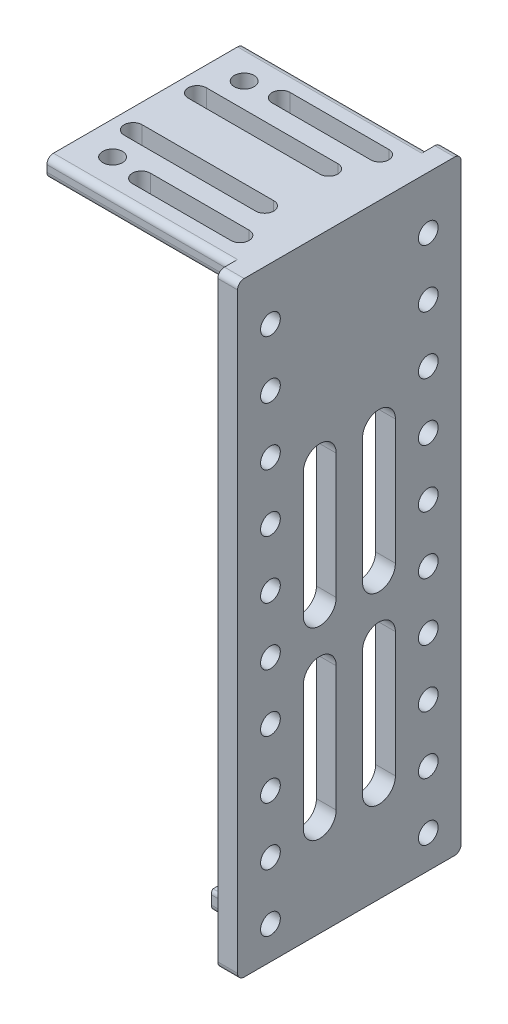
SolidWorks part; units mm, degrees
ref_plane "前视基准面" through (0, 0, 0) normal (0, 0, 1) x (1, 0, 0)
ref_plane "上视基准面" through (0, 0, 0) normal (0, 1, 0) x (1, 0, 0)
ref_plane "右视基准面" through (0, 0, 0) normal (1, 0, 0) x (0, 0, -1)
other "Configuration Table"
sketch "草图1" plane through (0, 0, 0) normal (0, 1, 0) x (1, 0, 0)
  line L0 (0, 12) -> (5, 12) construction
  line L1 (-1, 15) -> (1, 15) construction
  line L2 (-1, 15) -> (-1, 9) construction
  line L3 (-1, 9) -> (1, 9) construction
  line L4 (1, 15) -> (1, 9) construction
  line L5 (-1, 15) -> (1, 9) construction
  line L6 (-1, 9) -> (1, 15) construction
  line L7 (-1, -15) -> (1, -15) construction
  line L8 (-1, -15) -> (-1, -9) construction
  line L9 (-1, -9) -> (1, -9) construction
  line L10 (1, -15) -> (1, -9) construction
  line L11 (-1, -15) -> (1, -9) construction
  line L12 (-1, -9) -> (1, -15) construction
  line L13 (1, 14.5) -> (9, 14.5) construction
  line L14 (1, 14.5) -> (1, 9.5) construction
  line L15 (1, 9.5) -> (9, 9.5) construction
  line L16 (9, 14.5) -> (9, 9.5) construction
  line L17 (1, 14.5) -> (9, 9.5) construction
  line L18 (1, 9.5) -> (9, 14.5) construction
  line L19 (0, 0) -> (0, 9) construction
  line L20 (0, 12) -> (-5, 12) construction
  line L21 (-10.5, 0) -> (0, 0) construction
  line L22 (-9, 14.5) -> (-1, 14.5) construction
  line L23 (-9, 14.5) -> (-9, 9.5) construction
  line L24 (-9, 9.5) -> (-1, 9.5) construction
  line L25 (-1, 14.5) -> (-1, 9.5) construction
  line L26 (-9, 14.5) -> (-1, 9.5) construction
  line L27 (-9, 9.5) -> (-1, 14.5) construction
  line L33 (-12, -17) -> (-9, -17)
  line L34 (-12, -17) -> (-12, 17)
  line L35 (-12, 17) -> (-9, 17)
  line L36 (-9, -17) -> (-9, 17)
  line L37 (-12, -17) -> (-9, 17) construction
  line L38 (-12, 17) -> (-9, -17) construction
  circle A0 centre (0, 0) radius 9 construction
  circle A1 centre (0, 0) radius 12 construction
  point P4 (0, 12)
  point P9 (0, -12)
  point P14 (5, 12)
  point P28 (-10.5, 0)
  dimension "D1" = 18
  dimension "D2" = 24
  dimension "D3" = 6
  dimension "D4" = 2
  dimension "D5" = 8
  dimension "D6" = 5
  dimension "D7" = 8
  dimension "D8" = 5
  dimension "D9" = 3
  dimension "D10" = 5
extrude "凸台-拉伸1" add sketch "草图1" along normal blind 92
sketch "草图2" plane through (0, 0, 0) normal (0, -1, 0) x (1, 0, 0)
  line L0 (-12, -17) -> (-12, 17) construction
  line L1 (-20, 10) -> (-12, 10)
  line L2 (-20, 10) -> (-20, -10)
  line L3 (-20, -10) -> (-12, -10)
  line L4 (-12, 10) -> (-12, -10)
  line L5 (-20, 10) -> (-12, -10) construction
  line L6 (-20, -10) -> (-12, 10) construction
  line L7 (-16, 0) -> (0, 0) construction
  line L8 (-16, 5) -> (-16, -5) construction
  circle A0 centre (-16, 5) radius 1.5
  circle A1 centre (-16, -5) radius 1.5
  point P0 (-16, 0)
  point P14 (-16, 0)
  dimension "D5" = 3
  dimension "D1" = 20
  dimension "D2" = 20
  dimension "D3" = 10
  dimension "D4" = 16
extrude "凸台-拉伸2" add sketch "草图2" against normal blind 3
sketch "草图10" plane through (0, 92, 0) normal (0, 1, 0) x (1, 0, 0)
  line L0 (-26, 0) -> (0, 0) construction
  line L1 (-40, -15) -> (-12, -15)
  line L2 (-40, -15) -> (-40, 15)
  line L3 (-40, 15) -> (-12, 15)
  line L4 (-12, -15) -> (-12, 15)
  line L5 (-40, -15) -> (-12, 15) construction
  line L6 (-40, 15) -> (-12, -15) construction
  line L8 (-35, 10) -> (-35, -10) construction
  line L9 (-35, 0) -> (-26, 0) construction
  line L10 (-12, 17) -> (-12, -17) construction
  circle A0 centre (-35, 10) radius 1.5
  circle A1 centre (-35, -10) radius 1.5
  point P0 (-26, 0)
  dimension "D5" = 3
  dimension "D1" = 30
  dimension "D2" = 40
  dimension "D3" = 20
  dimension "D4" = 5
extrude "凸台-拉伸6" add sketch "草图10" against normal blind 3
sketch "草图11" plane through (0, 0, 0) normal (0, 0, 1) x (1, 0, 0)
  line L1 (-40, 89) -> (-12, 89) construction
  line L3 (-12, 69) -> (-12, 89)
  line L4 (-12, 89) -> (-27, 89)
  line L5 (-27, 89) -> (-15, 69)
  line L6 (-15, 69) -> (-12, 69)
  dimension "D1" = 20
  dimension "D2" = 15
  dimension "D3" = 3
extrude "凸台-拉伸7" add sketch "草图11" along normal mid plane 3
chamfer "倒角3" distance 3 angle 45 3 edges at (-12, 79, -1.5) (-12, 69, 0) (-12, 79, 1.5)
sketch "草图9" plane through (-12, 0, 0) normal (-1, 0, 0) x (0, 0, 1)
  line L0 (0, 0) -> (0, 92) construction
  line L2 (10, 0) -> (-10, 0) construction
  line L5 (17, 92) -> (-17, 92) construction
  line L6 (15, 92) -> (17, 92) construction
  circle A0 centre (12, 5) radius 1.5
  circle A1 centre (12, 13.7778) radius 1.5
  circle A2 centre (12, 22.5556) radius 1.5
  circle A3 centre (12, 31.3333) radius 1.5
  circle A4 centre (12, 40.1111) radius 1.5
  circle A5 centre (12, 48.8889) radius 1.5
  circle A6 centre (12, 57.6667) radius 1.5
  circle A7 centre (12, 66.4444) radius 1.5
  circle A8 centre (12, 75.2222) radius 1.5
  circle A9 centre (12, 84) radius 1.5
  circle A10 centre (-12, 84) radius 1.5
  circle A11 centre (-12, 75.2222) radius 1.5
  circle A12 centre (-12, 66.4444) radius 1.5
  circle A13 centre (-12, 57.6667) radius 1.5
  circle A14 centre (-12, 48.8889) radius 1.5
  circle A15 centre (-12, 40.1111) radius 1.5
  circle A16 centre (-12, 31.3333) radius 1.5
  circle A17 centre (-12, 22.5556) radius 1.5
  circle A18 centre (-12, 13.7778) radius 1.5
  circle A19 centre (-12, 5) radius 1.5
  dimension "D2" = 3
  dimension "D1" = 24
  dimension "D3" = 5
  dimension "D5" = 8
  dimension "D4" = 10
extrude "切除-拉伸2" cut sketch "草图9" against normal blind 3
chamfer "倒角4" distance 8 angle 45 1 edges at (-12, 3, 0)
sketch "草图12" plane through (-12, 0, 0) normal (-1, 0, 0) x (0, 0, 1)
  circle A0 centre (-12, 5) radius 3
  circle A2 centre (12, 5) radius 3
  dimension "D1" = 6
extrude "切除-拉伸3" cut sketch "草图12" along normal blind 17
sketch "草图13" plane through (0, 0, 0) normal (0, -1, 0) x (1, 0, 0)
  circle A0 centre (-16, 5) radius 3
  circle A1 centre (-16, -5) radius 3
  dimension "D1" = 6
extrude "切除-拉伸4" cut sketch "草图13" against normal blind 17 from offset 3 offset against normal yes
fillet "圆角1" radius 1 20 edges at (-16, 0, -10) (-10.5, 0, -17) (-10.5, 92, -17) (-26, 92, -15) (-26, 89, -15) (-13.5, 89, -3) (-13.5, 67.5, -3) (-13.5, 67.5, 3) (-13.5, 89, 3) (-26, 89, 15) (-26, 92, 15) (-10.5, 92, 17) (-16, 0, 10) (-16, 2.7639, 10) (-13.882, 7.2361, 10) (-13.882, 9.118, 10) (-13.882, 9.118, -10) (-13.882, 7.2361, -10) (-16, 2.7639, -10) (-10.5, 0, 17)
sketch "草图14" plane through (-12, 0, 0) normal (-1, 0, 0) x (0, 0, 1)
  line L0 (-4.5, 34) -> (-4.5, 15) construction
  line L1 (-2, 34) -> (-2, 15)
  line L2 (-7, 34) -> (-7, 15)
  line L3 (4.5, 34) -> (4.5, 15) construction
  line L4 (7, 34) -> (7, 15)
  line L5 (2, 34) -> (2, 15)
  line L6 (0, 0) -> (0, 92) construction
  line L7 (-14, 92) -> (14, 92) construction
  line L8 (-4.5, 15) -> (4.5, 15) construction
  line L9 (9, 0) -> (16, 0) construction
  line L10 (0, 38.5) -> (17, 38.5) construction
  line L11 (17, 91) -> (17, 1) construction
  line L12 (-4.5, 43) -> (-4.5, 62) construction
  line L13 (-2, 43) -> (-2, 62)
  line L14 (-7, 43) -> (-7, 62)
  line L15 (4.5, 43) -> (4.5, 62) construction
  line L16 (7, 43) -> (7, 62)
  line L17 (2, 43) -> (2, 62)
  arc A0 (-2, 34) -> (-7, 34) centre (-4.5, 34) ccw
  arc A1 (-7, 15) -> (-2, 15) centre (-4.5, 15) ccw
  arc A2 (7, 34) -> (2, 34) centre (4.5, 34) ccw
  arc A3 (2, 15) -> (7, 15) centre (4.5, 15) ccw
  arc A4 (-2, 43) -> (-7, 43) centre (-4.5, 43) cw
  arc A5 (-7, 62) -> (-2, 62) centre (-4.5, 62) cw
  arc A6 (7, 43) -> (2, 43) centre (4.5, 43) cw
  arc A7 (2, 62) -> (7, 62) centre (4.5, 62) cw
  point P2 (-4.5, 24.5)
  point P7 (4.5, 24.5)
  point P29 (-4.5, 52.5)
  point P36 (4.5, 52.5)
  dimension "D1" = 2.5
  dimension "D2" = 4
  dimension "D3" = 19
  dimension "D4" = 15
  dimension "D5" = 9
extrude "切除-拉伸5" cut sketch "草图14" against normal blind 10
sketch "草图15" plane through (0, 89, 0) normal (0, -1, 0) x (1, 0, 0)
  line L6 (-40, -14) -> (-40, 14) construction
  line L8 (-40, 0) -> (0, 0) construction
  line L9 (-30, 10.625) -> (-15, 10.625) construction
  line L10 (-30, 12) -> (-15, 12)
  line L11 (-30, 9.25) -> (-15, 9.25)
  line L12 (-37, 4.875) -> (-17, 4.875) construction
  line L13 (-37, 6.25) -> (-17, 6.25)
  line L14 (-37, 3.5) -> (-17, 3.5)
  line L15 (-16.4142, 1.5) -> (-27, 1.5) construction
  line L16 (-12, 14) -> (-40, 14) construction
  line L17 (-30, -10.625) -> (-15, -10.625) construction
  line L18 (-30, -12) -> (-15, -12)
  line L19 (-30, -9.25) -> (-15, -9.25)
  line L20 (-37, -4.875) -> (-17, -4.875) construction
  line L21 (-37, -6.25) -> (-17, -6.25)
  line L22 (-37, -3.5) -> (-17, -3.5)
  arc A0 (-30, 12) -> (-30, 9.25) centre (-30, 10.625) ccw
  arc A1 (-15, 9.25) -> (-15, 12) centre (-15, 10.625) ccw
  arc A2 (-37, 6.25) -> (-37, 3.5) centre (-37, 4.875) ccw
  arc A3 (-17, 3.5) -> (-17, 6.25) centre (-17, 4.875) ccw
  arc A4 (-30, -12) -> (-30, -9.25) centre (-30, -10.625) cw
  arc A5 (-15, -9.25) -> (-15, -12) centre (-15, -10.625) cw
  arc A6 (-37, -6.25) -> (-37, -3.5) centre (-37, -4.875) cw
  arc A7 (-17, -3.5) -> (-17, -6.25) centre (-17, -4.875) cw
  point P0 (-17.3194, 4.875)
  point P3 (-22.5, -10.625)
  point P5 (-22.5, 10.625)
  point P22 (-27, 4.875)
  point P31 (-26.7133, 4.875)
  point P33 (-30.1764, 9.8386)
  point P35 (-27, -4.875)
  dimension "D8" = 15
  dimension "D1" = 20
  dimension "D2" = 3
  dimension "D5" = 2
  dimension "D6" = 3
  dimension "D7" = 2
  dimension "D9" = 10
extrude "切除-拉伸6" cut sketch "草图15" against normal blind 10
